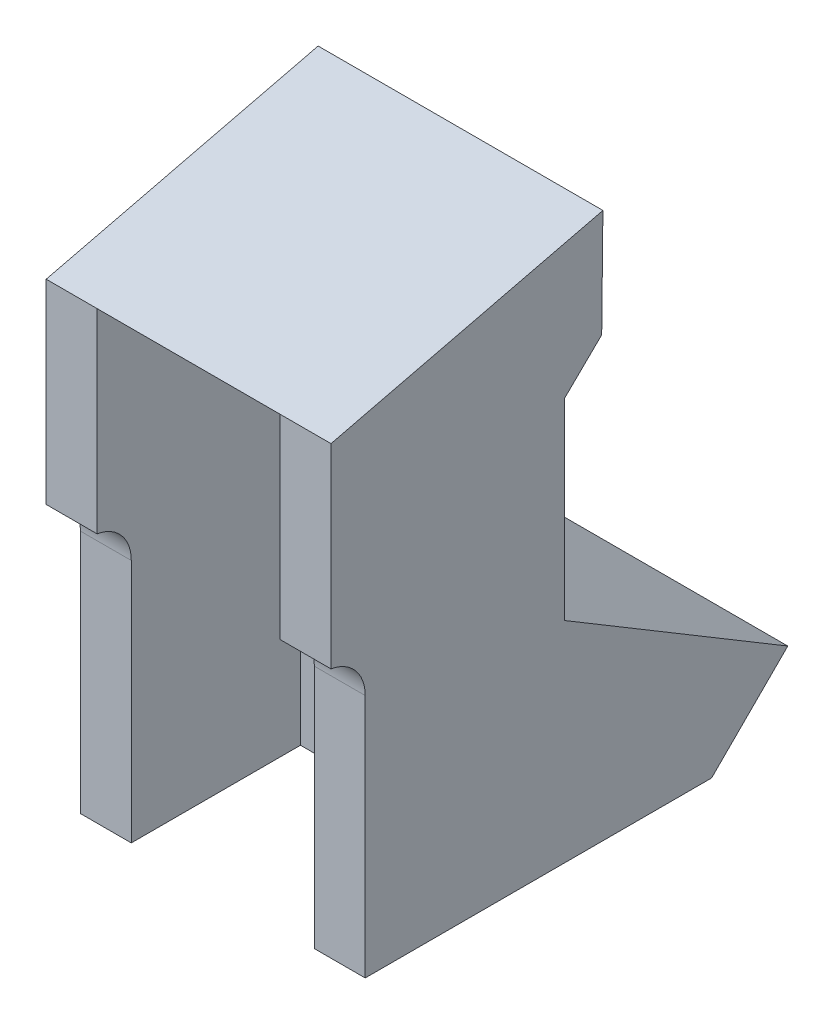
SolidWorks part; units mm, degrees
ref_plane "Front Plane" through (0, 0, 0) normal (0, 0, 1) x (1, 0, 0)
ref_plane "Top Plane" through (0, 0, 0) normal (0, 1, 0) x (1, 0, 0)
ref_plane "Right Plane" through (0, 0, 0) normal (1, 0, 0) x (0, 0, -1)
sketch "Sketch4" plane through (0, 0, 0) normal (1, 0, 0) x (0, 0, -1)
  line L0 (-4.4218, 9.1497) -> (14.3537, 13.7075)
  line L1 (14.3537, 13.7075) -> (5.3741, 4.928)
  line L2 (5.3741, 4.928) -> (5.3741, -4.5278)
  line L3 (5.3741, -4.5278) -> (22.6052, -14.8503)
  line L4 (22.6052, -14.8503) -> (-4.4218, -14.8503)
  line L5 (-4.4218, -0.8503) -> (-4.4218, -14.8503)
  line L6 (-4.4218, 9.1497) -> (-6.1039, 8.7413)
  line L7 (-6.1039, 8.7413) -> (-6.1039, -0.8503)
  line L8 (-6.1039, -0.8503) -> (-4.4218, -0.8503)
  dimension "D1" = 10
  dimension "D2" = 14
extrude "Boss-Extrude5" add sketch "Sketch4" along normal blind 14
sketch "Sketch6" plane through (0, 0, 6.1039) normal (0, 0, 1) x (1, 0, 0)
  line L0 (14, 8.7413) -> (0, 8.7413) construction
  line L1 (2.5, 8.7413) -> (11.5, 8.7413)
  line L2 (2.5, 8.7413) -> (2.5, -14.8503)
  line L3 (2.5, -14.8503) -> (11.5, -14.8503)
  line L4 (11.5, 8.7413) -> (11.5, -14.8503)
  line L5 (14, -14.8503) -> (0, -14.8503) construction
  line L6 (0, 8.7413) -> (0, -0.8503) construction
  line L7 (14, 8.7413) -> (14, -0.8503) construction
  dimension "D1" = 2.5
  dimension "D2" = 2.5
extrude "Cut-Extrude1" cut sketch "Sketch6" against normal blind 10
fillet "Fillet1" radius 2 2 edges at (1.25, -0.8503, 4.4218) (12.75, -0.8503, 4.4218)
chamfer "Chamfer1" distance 10 angle 45 2 edges at (7, -14.8503, -22.6052) (7, 13.7075, -14.3537) first distance on face at (7, -14.8503, -4.4144) first distance on face at (7, 9.3177, -9.8639)
